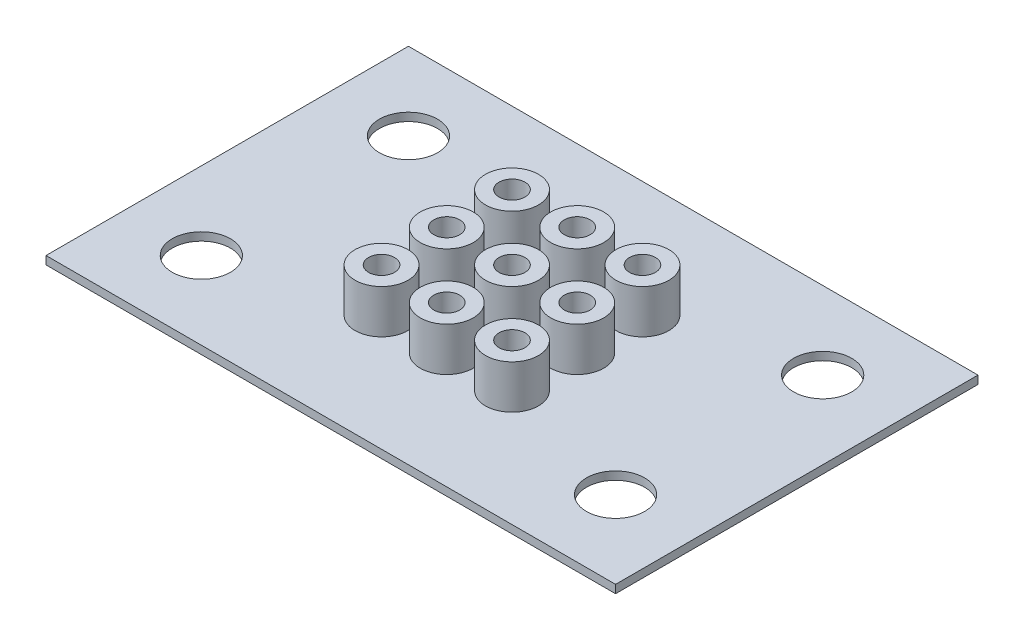
SolidWorks part; units mm, degrees
ref_plane "Front Plane" through (0, 0, 0) normal (0, 0, 1) x (1, 0, 0)
ref_plane "Top Plane" through (0, 0, 0) normal (0, 1, 0) x (1, 0, 0)
ref_plane "Right Plane" through (0, 0, 0) normal (1, 0, 0) x (0, 0, -1)
sketch "Sketch1" plane through (0, 0, 0) normal (0, 1, 0) x (1, 0, 0)
  line L0 (9.525, 34.925) -> (0, 34.925) construction
  line L1 (0, 0) -> (69.85, 0)
  line L2 (0, 0) -> (0, 44.45)
  line L3 (0, 44.45) -> (69.85, 44.45)
  line L4 (69.85, 0) -> (69.85, 44.45)
  line L5 (9.525, 34.925) -> (60.325, 34.925) construction
  line L6 (9.525, 34.925) -> (9.525, 9.525) construction
  line L7 (9.525, 9.525) -> (60.325, 9.525) construction
  line L8 (60.325, 34.925) -> (60.325, 9.525) construction
  line L9 (9.525, 34.925) -> (9.525, 44.45) construction
  line L10 (34.925, 22.225) -> (34.925, 30.225) construction
  circle A0 centre (9.525, 34.925) radius 3.5687
  circle A1 centre (60.325, 34.925) radius 3.5687
  circle A2 centre (9.525, 9.525) radius 3.5687
  circle A3 centre (60.325, 9.525) radius 3.5687
  circle A4 centre (34.925, 22.225) radius 1.25
  circle A5 centre (42.925, 22.225) radius 1.25
  circle A6 centre (42.925, 30.225) radius 1.25
  circle A7 centre (34.925, 30.225) radius 1.25
  circle A8 centre (26.925, 22.225) radius 1.25
  circle A9 centre (26.925, 30.225) radius 1.25
  circle A10 centre (34.925, 30.225) radius 1.25
  circle A11 centre (42.925, 22.225) radius 1.25
  circle A12 centre (42.925, 14.225) radius 1.25
  circle A13 centre (34.925, 14.225) radius 1.25
  circle A14 centre (26.925, 22.225) radius 1.25
  circle A15 centre (26.925, 14.225) radius 1.25
  circle A16 centre (34.925, 14.225) radius 1.25
  point P13 (34.925, 34.925)
  point P14 (34.925, 44.45)
  point P20 (69.85, 22.225)
  dimension "D5" = 7.1374
  dimension "D6" = 2.5
  dimension "D1" = 69.85
  dimension "D2" = 44.45
  dimension "D3" = 50.8
  dimension "D4" = 25.4
  dimension "D9" = 8
  dimension "D7" = 2
  dimension "D8" = 2
  dimension "D10" = 2
  dimension "D11" = 2
  dimension "D12" = 2
  dimension "D13" = 2
  dimension "D14" = 2
  dimension "D15" = 2
extrude "Boss-Extrude1" add sketch "Sketch1" along normal blind 1 contours L1 L4 L3 L2 A15 A13 A12 A9 A8 A7 A6 A5 A4 A3 A2 A1 A0 region at (0.8279, 0, -22.225)
sketch "Sketch2" plane through (0, 1, 0) normal (0, 1, 0) x (1, 0, 0)
  line L0 (34.925, 22.225) -> (34.925, 30.225) construction
  circle A0 centre (34.925, 22.225) radius 3.25
  circle A1 centre (34.925, 22.225) radius 1.59
  circle A2 centre (42.925, 22.225) radius 3.25
  circle A3 centre (42.925, 22.225) radius 1.59
  circle A4 centre (42.925, 30.225) radius 3.25
  circle A5 centre (42.925, 30.225) radius 1.59
  circle A6 centre (34.925, 30.225) radius 3.25
  circle A7 centre (34.925, 30.225) radius 1.59
  circle A8 centre (42.925, 22.225) radius 1.59
  circle A9 centre (42.925, 22.225) radius 3.25
  circle A10 centre (42.925, 14.225) radius 1.59
  circle A11 centre (42.925, 14.225) radius 3.25
  circle A12 centre (34.925, 14.225) radius 1.59
  circle A13 centre (34.925, 14.225) radius 3.25
  circle A14 centre (26.925, 22.225) radius 3.25
  circle A15 centre (26.925, 22.225) radius 1.59
  circle A16 centre (26.925, 30.225) radius 3.25
  circle A17 centre (26.925, 30.225) radius 1.59
  circle A18 centre (34.925, 30.225) radius 3.25
  circle A19 centre (34.925, 30.225) radius 1.59
  circle A20 centre (26.925, 22.225) radius 1.59
  circle A21 centre (26.925, 22.225) radius 3.25
  circle A22 centre (26.925, 14.225) radius 1.59
  circle A23 centre (26.925, 14.225) radius 3.25
  circle A24 centre (34.925, 14.225) radius 1.59
  circle A25 centre (34.925, 14.225) radius 3.25
  dimension "D1" = 3.18
  dimension "D2" = 6.5
  dimension "D5" = 8
  dimension "D3" = 2
  dimension "D4" = 2
  dimension "D6" = 2
  dimension "D7" = 2
  dimension "D8" = 2
  dimension "D9" = 2
extrude "Boss-Extrude2" add sketch "Sketch2" along normal blind 5.35 contours A16 A17 | A14 A15 | A6 A7 | A4 A5 | A2 A3 | A1 A0 | A23 A22 | A13 A12 | A11 A10 region at (31.7669, 1, -22.225) region at (39.7669, 1, -22.225) region at (39.7669, 1, -30.225) region at (31.7669, 1, -30.225) region at (39.7669, 1, -14.225) region at (31.7669, 1, -14.225) region at (23.7669, 1, -22.225) region at (23.7669, 1, -30.225) region at (23.7669, 1, -14.225)
